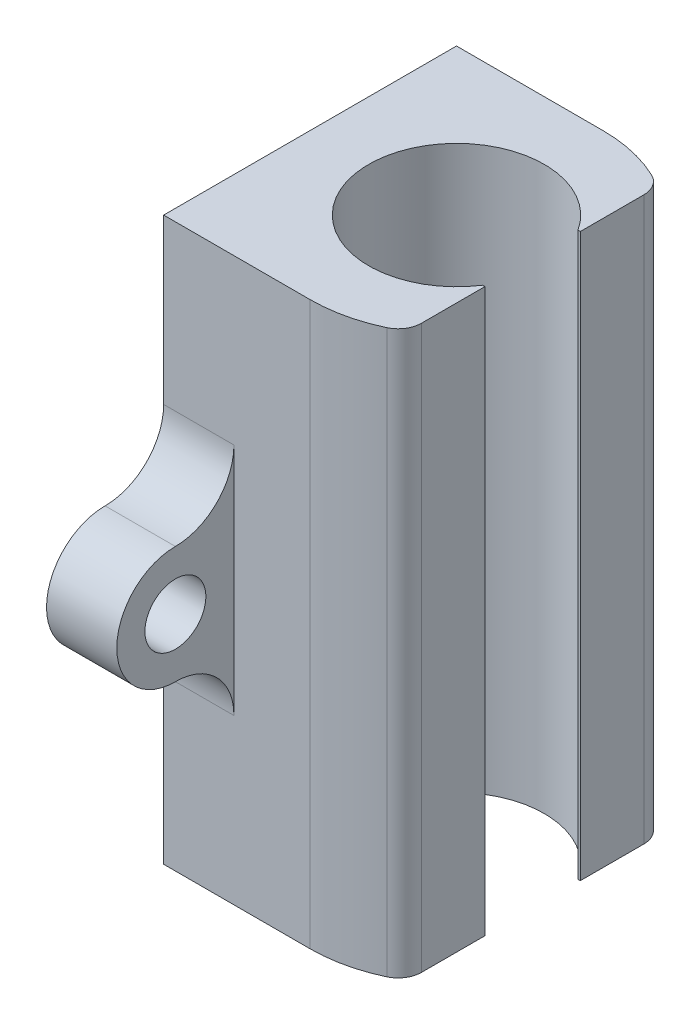
SolidWorks part; units mm, degrees
material "PET"
ref_plane "Front Plane" through (0, 0, 0) normal (0, 0, 1) x (1, 0, 0)
ref_plane "Top Plane" through (0, 0, 0) normal (0, 1, 0) x (1, 0, 0)
ref_plane "Right Plane" through (0, 0, 0) normal (1, 0, 0) x (0, 0, -1)
sketch "Sketch1" plane through (0, 0, 0) normal (0, 1, 0) x (1, 0, 0)
  line L1 (0, 12.5) -> (-12.5, 12.5)
  line L3 (0, -12.5) -> (-12.5, -12.5)
  line L4 (-12.5, 12.5) -> (-12.5, -12.5)
  circle A0 centre (0, 0) radius 7.5
  arc A1 (0, -12.5) -> (0, 12.5) centre (0, 0) ccw
  dimension "D1" = 15
  dimension "D2" = 12.5
  dimension "D3" = 12.5
extrude "Boss-Extrude1" add sketch "Sketch1" along normal blind 48
sketch "Sketch2" plane through (-12.5, 0, 0) normal (-1, 0, 0) x (0, 0, 1)
  line L2 (-12.5, 24) -> (12.5, 24) construction
  line L3 (-12.5, 48) -> (-12.5, 0) construction
  line L4 (12.5, 48) -> (12.5, 0) construction
  line L5 (-17.5, 29) -> (-12.5, 29)
  line L6 (-17.5, 19) -> (-12.5, 19)
  line L7 (-12.5, 19) -> (-12.5, 29)
  line L8 (17.5, 29) -> (12.5, 29)
  line L9 (12.5, 29) -> (12.5, 19)
  line L10 (12.5, 19) -> (17.5, 19)
  arc A0 (-17.5, 29) -> (-17.5, 19) centre (-17.5, 24) ccw
  arc A1 (17.5, 19) -> (17.5, 29) centre (17.5, 24) ccw
  dimension "D1" = 10
  dimension "D2" = 10
extrude "Boss-Extrude2" add sketch "Sketch2" against normal blind 6
sketch "Sketch3" plane through (-12.5, 0, 0) normal (-1, 0, 0) x (0, 0, 1)
  line L0 (-12.5, 48) -> (-12.5, 0) construction
  circle A0 centre (-17.5, 24) radius 2.6
  circle A1 centre (17.5, 24) radius 2.6
  arc A2 (-17.5, 29) -> (-17.5, 19) centre (-17.5, 24) ccw construction
  dimension "D1" = 5.2
  dimension "D2" = 5.2
extrude "Cut-Extrude1" cut sketch "Sketch3" against normal blind 6
fillet "Fillet6" radius 5 1 edges at (-9.5, 19, -12.5)
fillet "Fillet7" radius 5 3 edges at (-9.5, 19, 12.5) (-9.5, 29, 12.5) (-9.5, 29, -12.5)
sketch "Sketch5" plane through (0, 0, 0) normal (0, -1, 0) x (1, 0, 0)
  line L0 (0, -12.5) -> (-12.5, -12.5) construction
  line L1 (12.5, 12.5) -> (6.5, 12.5)
  line L2 (12.5, 12.5) -> (12.5, -12.5)
  line L3 (12.5, -12.5) -> (6.5, -12.5)
  line L4 (6.5, 12.5) -> (6.5, 4.0694)
  line L5 (-12.5, 12.5) -> (0, 12.5) construction
  line L6 (6.5, -4.0694) -> (6.5, -12.5)
  line L7 (6.5, 4.0694) -> (6.3, 4.0694)
  line L9 (6.5, -4.0694) -> (6.3, -4.0694)
  line L10 (6.3, 4.0694) -> (6.3, -4.0694)
  arc A0 (0, -12.5) -> (0, 12.5) centre (0, 0) ccw construction
  circle A1 centre (0, 0) radius 7.5 construction
  point P15 (6.3, 0)
  point P16 (12.5, 0)
  dimension "D1" = 6
  dimension "D2" = 0.2
  dimension "D3" = 0
extrude "Cut-Extrude4" cut sketch "Sketch5" against normal through all
fillet "Fillet9" radius 2 1 edges at (6.5, 24, 10.6771)
fillet "Fillet11" radius 2 1 edges at (6.5, 24, -10.6771)
